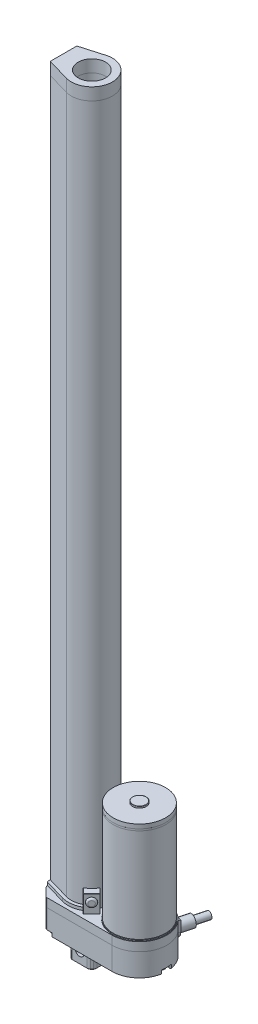
SolidWorks part; units mm, degrees
note: The reader was unsure of these and kept them because the rebuilt part matched: shared geometry of "Sketch1<3>", "Sketch41<11>", "Sketch41<12>", "Sketch45<3>".
ref_plane "Front Plane" through (0, 0, 0) normal (0, 0, 1) x (1, 0, 0)
ref_plane "Top Plane" through (0, 0, 0) normal (0, 1, 0) x (1, 0, 0)
ref_plane "Right Plane" through (0, 0, 0) normal (1, 0, 0) x (0, 0, -1)
sketch "Sketch1" plane through (0, 0, 0) normal (0, 1, 0) x (1, 0, 0)
  line L0 (0, 32.639) -> (7.239, 39.878)
  line L1 (7.239, 0) -> (55.118, 0)
  line L2 (0, 7.239) -> (0, 32.639)
  line L3 (7.239, 39.878) -> (55.118, 39.878)
  line L4 (7.239, 0) -> (0, 7.239)
  arc A0 (55.118, 0) -> (55.118, 39.878) centre (55.118, 19.939) ccw
  point P0 (0, 0)
  point P2 (0, 39.878)
  dimension "D1" = 55.118
  dimension "D2" = 39.878
extrude "Boss-Extrude1" add sketch "Sketch1" along normal blind 6.35
sketch "Sketch6" plane through (0, 6.35, 0) normal (0, 1, 0) x (1, 0, 0)
  circle A0 centre (55.118, 19.939) radius 19.431
extrude "Boss-Extrude4" add sketch "Sketch6" along normal blind 0.762 separate body contours A0
sketch "Sketch7" plane through (0, 7.112, 0) normal (0, 1, 0) x (1, 0, 0)
  circle A0 centre (55.118, 19.939) radius 19.05
  dimension "D1" = 38.1
extrude "Boss-Extrude5" add sketch "Sketch7" along normal blind 68.326 separate body
sketch "Sketch8" plane through (0, 75.438, 0) normal (0, 1, 0) x (1, 0, 0)
  circle A0 centre (55.118, 19.939) radius 4.953
  dimension "D1" = 9.906
fillet "Fillet6" radius 5.08 2 edges at (0, 3.175, -7.239) (0, 3.175, -32.639)
fillet "Fillet7" radius 1.905 2 edges at (7.239, 3.175, -39.878) (7.239, 3.175, 0)
sketch "Sketch15" plane through (0, 6.35, 0) normal (0, 1, 0) x (1, 0, 0)
  line L0 (35.5603, 29.0153) -> (35.5603, 29.0265)
  line L2 (0, 30.5348) -> (0, 9.3432) construction
  line L3 (0, 19.939) -> (0, 10.2869)
  line L4 (0, 19.939) -> (0, 29.591)
  line L5 (0, 10.2869) -> (16.412, 5.5423)
  line L7 (35.5603, 10.8628) -> (35.5603, 10.8515)
  line L10 (0, 29.591) -> (16.4119, 34.3357)
  arc A0 (16.412, 5.5423) -> (16.4119, 34.3357) centre (20.574, 19.939) ccw
ref_plane "Plane4" through (13.8375, 0, -51.6424) normal (0.2588, 0, -0.9659) x (0, -1, 0)
ref_plane "Plane5" through (12.5227, 0, -46.7355) normal (0.2588, 0, -0.9659) x (0, -1, 0)
sketch "Sketch23" plane through (12.5227, 0, -46.7355) normal (0.2588, 0, -0.9659) x (0, -1, 0)
  line L0 (-6.35, -67.5103) -> (-6.35, -28.6483) construction
  line L1 (-2.032, -53.8839) -> (5.588, -53.8839)
  line L2 (-2.032, -53.8839) -> (-2.032, -42.4539)
  line L3 (-2.032, -42.4539) -> (5.588, -42.4539)
  arc A0 (5.588, -53.8839) -> (5.588, -42.4539) centre (5.588, -48.1689) ccw
  dimension "D1" = 11.43
  dimension "D2" = 7.62
  dimension "D3" = 4.318
extrude "Boss-Extrude15" add sketch "Sketch23" along normal blind 6.35
sketch "Sketch24" plane through (14.1662, 0, -52.8692) normal (0.2588, 0, -0.9659) x (-0.9659, 0, -0.2588)
  circle A0 centre (-48.1689, -5.588) radius 4.064
  dimension "D1" = 8.128
extrude "Boss-Extrude16" add sketch "Sketch24" along normal blind 10.16
sketch "Sketch25" plane through (16.7959, 0, -62.683) normal (0.2588, 0, -0.9659) x (-0.9659, 0, -0.2588)
  circle A0 centre (-48.1689, -5.588) radius 2.54
  dimension "D1" = 5.08
extrude "Boss-Extrude17" add sketch "Sketch25" along normal blind 10.16
extrude "Boss-Extrude19" add sketch "Sketch1<3>" against normal blind 16.51 separate body
sketch "Sketch1<3>" plane through (0, 0, 0) normal (0, 1, 0) x (1, 0, 0) same geometry as "Sketch1"
fillet "Fillet13" radius 1.905 2 edges at (7.239, -8.255, 0) (7.239, -8.255, -39.878)
fillet "Fillet14" radius 5.08 2 edges at (0, -8.255, -32.639) (0, -8.255, -7.239)
sketch "Sketch26" plane through (0, -16.51, 0) normal (0, -1, 0) x (-1, 0, 0)
  line L4 (-20.574, 28.829) -> (-11.684, 28.829)
  line L5 (-20.574, 28.829) -> (-29.464, 28.829)
  line L6 (-11.684, 28.829) -> (-11.684, 11.049)
  line L7 (-11.684, 11.049) -> (-29.464, 11.049)
  line L8 (-29.464, 11.049) -> (-29.464, 28.829)
extrude "Boss-Extrude20" add sketch "Sketch26" along normal blind 18.796 separate body
chamfer "Chamfer1" distance 2.54 angle 45 4 edges at (29.464, -25.908, -28.829) (29.464, -25.908, -11.049) (11.684, -25.908, -11.049) (11.684, -25.908, -28.829)
fillet "Fillet15" radius 2.54 8 edges at (11.684, -25.908, -13.589) (14.224, -25.908, -11.049) (26.924, -25.908, -11.049) (29.464, -25.908, -13.589) (29.464, -25.908, -26.289) (26.924, -25.908, -28.829) (11.684, -25.908, -26.289) (14.224, -25.908, -28.829)
chamfer "Chamfer2" distance 0.762 angle 45 16 edges at (14.3041, -35.306, -11.2423) (20.574, -35.306, -11.049) (26.8439, -35.306, -11.2423) (28.194, -35.306, -12.319) (29.2707, -35.306, -13.6691) (29.464, -35.306, -19.939) (29.2707, -35.306, -26.2089) (28.194, -35.306, -27.559) (26.8439, -35.306, -28.6357) (20.574, -35.306, -28.829) (14.3041, -35.306, -28.6357) (12.954, -35.306, -27.559) (11.8773, -35.306, -26.2089) (11.684, -35.306, -19.939) (11.8773, -35.306, -13.6691) (12.954, -35.306, -12.319)
sketch "Sketch27" plane through (0, 0, -11.049) normal (0, 0, 1) x (1, 0, 0)
  circle A0 centre (20.574, -26.67) radius 3.175
extrude "Cut-Extrude3" cut sketch "Sketch27" against normal blind 19.05
sketch "Sketch28" plane through (0, 75.438, 0) normal (0, 1, 0) x (1, 0, 0)
  circle A0 centre (55.118, 19.939) radius 19.05
extrude "Boss-Extrude22" add sketch "Sketch28" along normal blind 1.27 separate body
sketch "Sketch29" plane through (0, 76.708, 0) normal (0, 1, 0) x (1, 0, 0)
  circle A0 centre (55.118, 19.939) radius 19.05
extrude "Boss-Extrude24" add sketch "Sketch29" along normal blind 3.048 separate body contours A0
extrude "Boss-Extrude25" add sketch "Sketch8" along normal blind 1.27 from surface at 4.318 contours A0 starting at face at (55.118, 79.756, -0.889)
fillet "Fillet16" radius 0.2286 1 edges at (55.118, 81.026, -14.986)
extrude "Boss-Extrude26" add sketch "Sketch15" along normal blind 508.381 separate body contours L5 A0 L10 L4 L3
sketch "Sketch32" plane through (0, 514.731, 0) normal (0, 1, 0) x (1, 0, 0)
  line L0 (0, 10.2869) -> (0, 29.591)
  line L1 (0, 29.591) -> (16.4119, 34.3357)
  line L2 (0, 10.2869) -> (16.412, 5.5423)
  arc A0 (16.412, 5.5423) -> (16.4119, 34.3357) centre (20.574, 19.939) ccw
  circle A1 centre (20.574, 19.939) radius 9.9695
  dimension "D1" = 19.939
extrude "Boss-Extrude27" add sketch "Sketch32" along normal blind 8.89 separate body
sketch "Sketch33" plane through (0, 523.621, 0) normal (0, 1, 0) x (1, 0, 0)
  circle A0 centre (20.574, 19.939) radius 10.033
  dimension "D1" = 20.066
sketch3d "3DSketch1" plane through (0, 0, 0) normal (0, 0, 1) x (1, 0, 0)
sketch "Sketch41" plane through (0, 6.35, 0) normal (0, 1, 0) x (1, 0, 0)
  line L0 (16.4119, 34.3357) -> (0, 29.591)
  line L1 (37.5429, 9.0662) -> (33.7712, 12.8379)
  line L2 (0.2737, 32.0497) -> (15.777, 36.5318)
  line L3 (37.5429, 9.0662) -> (31.2567, 2.78)
  line L4 (0, 29.591) -> (0, 30.5348)
  line L5 (0, 30.5348) -> (0.2737, 32.0497)
  line L6 (-0.6349, 31.7871) -> (15.777, 36.5318) construction
  line L7 (0, 19.9389) -> (7.9017, 19.9389)
  line L8 (31.2567, 2.78) -> (27.426, 6.6107)
  line L9 (0, 10.2869) -> (0, 29.591) construction
  line L10 (0, 10.2869) -> (0, 9.3431)
  line L12 (37.5429, 30.8116) -> (33.7712, 27.0399)
  line L13 (37.5429, 30.8116) -> (31.2567, 37.0978)
  line L14 (31.2567, 37.0978) -> (27.426, 33.2671)
  line L15 (0, 9.3431) -> (0.2737, 7.8281)
  line L16 (0.2737, 7.8281) -> (15.777, 3.3461)
  line L17 (16.4119, 5.5422) -> (0, 10.2869)
  line L18 (-0.6349, 8.0908) -> (15.7771, 3.3462) construction
  line L19 (27.426, 33.2671) -> (29.1122, 34.9533)
  line L20 (0, 29.591) -> (16.4119, 34.3357) construction
  line L21 (0, 10.2869) -> (16.412, 5.5423) construction
  arc A0 (16.4119, 34.3357) -> (33.7712, 27.0399) centre (20.574, 19.939) cw
  arc A1 (15.777, 36.5318) -> (29.1122, 34.9533) centre (20.574, 19.939) cw
  arc A2 (16.4119, 34.3357) -> (16.412, 5.5423) centre (20.574, 19.939) cw construction
  arc A3 (15.777, 36.5318) -> (15.7771, 3.3462) centre (20.574, 19.939) cw construction
  arc A4 (16.4119, 34.3357) -> (27.426, 33.2671) centre (20.574, 19.939) cw
  arc A5 (15.777, 3.3461) -> (29.1122, 4.9245) centre (20.574, 19.9389) ccw
  arc A6 (16.4119, 5.5422) -> (33.7712, 12.8379) centre (20.574, 19.9389) ccw
  line M5 (0, 30.5348) -> (0, 9.3432)
  arc M6 (0, 9.3432) -> (1.4879, 5.7511) centre (5.08, 9.3432) ccw
extrude "Boss-Extrude30" add sketch "Sketch41" along normal blind 2.159 separate body contours A1 L2 L5 L0 A0 L14 M5
extrude "Boss-Extrude31" add sketch "Sketch41<11>" along normal blind 2.159 separate body contours A6 L17 L15 L16 A5 L8 M5 M6
sketch "Sketch41<11>" plane through (0, 6.35, 0) normal (0, 1, 0) x (1, 0, 0) same geometry as "Sketch41"
extrude "Boss-Extrude33" add sketch "Sketch41<12>" along normal blind 12.7 separate body contours L14 A0 L12 L13 | A6 L8 L3 L1
sketch "Sketch41<12>" plane through (0, 6.35, 0) normal (0, 1, 0) x (1, 0, 0) same geometry as "Sketch41"
fillet "Fillet17" radius 0.2286 5 edges at (35.657, 19.05, -28.9258) (29.3413, 19.05, -35.1825) (34.3998, 19.05, -33.9547) (37.5429, 12.7, -30.8116) (31.2567, 12.7, -37.0978)
fillet "Fillet18" radius 0.2286 5 edges at (35.657, 19.05, -10.9521) (29.3413, 19.05, -4.6954) (37.5429, 12.7, -9.0662) (34.3998, 19.05, -5.9231) (31.2567, 12.7, -2.78)
sketch "Sketch43" plane through (34.1773, 0, -34.1773) normal (0.7071, 0, -0.7071) x (-0.7071, 0, -0.7071)
  circle A0 centre (-0.3147, 13.7414) radius 3.175
extrude "Boss-Extrude34" add sketch "Sketch43" along normal blind 1.27 separate body
fillet "Fillet19" radius 1.27 1 edges at (33.0527, 13.7414, -37.0978)
sketch "Sketch44" plane through (14.2383, 0, 14.2383) normal (0.7071, 0, 0.7071) x (0.7071, 0, -0.7071)
  circle A0 centre (28.5126, 13.7414) radius 3.175
extrude "Boss-Extrude35" add sketch "Sketch44" along normal blind 1.27 separate body
fillet "Fillet20" radius 1.27 1 edges at (37.5429, 13.7414, -7.2702)
sketch "Sketch45" plane through (0, -16.51, 0) normal (0, -1, 0) x (1, 0, 0)
  line L0 (4.0845, -36.7235) -> (6.681, -39.32)
  line L2 (6.681, -39.32) -> (1.4879, -34.1269) construction
  line L4 (55.118, -39.878) -> (8.0281, -39.878) construction
  line L5 (11.3938, -39.878) -> (8.0281, -39.878)
  line L6 (11.3938, 0) -> (8.0281, 0)
  line L7 (4.0845, -3.1545) -> (6.681, -0.558)
  arc A0 (11.2821, -38.9146) -> (11.3938, -39.878) centre (11.8197, -39.3405) ccw
  arc A1 (11.2821, -38.9146) -> (5.0443, -35.9783) centre (8.8543, -35.9783) ccw
  arc A2 (11.2821, -0.9634) -> (11.3938, 0) centre (11.8197, -0.5375) cw
  arc A3 (5.0443, -35.9783) -> (4.0845, -36.7235) centre (4.1918, -35.871) cw
  arc A4 (5.0443, -3.8997) -> (4.0845, -3.1545) centre (4.1918, -4.007) ccw
  arc A5 (11.2821, -0.9634) -> (5.0443, -3.8997) centre (8.8543, -3.8997) cw
  arc A6 (55.118, -39.878) -> (55.118, 0) centre (55.118, -19.939) ccw construction
  arc A7 (73.6621, -16.9922) -> (73.6621, -22.8858) centre (71.247, -19.939) ccw
  arc A8 (73.6621, -22.8858) -> (74.7121, -23.6317) centre (73.8141, -23.7837) cw
  arc A9 (73.6621, -16.9922) -> (74.7121, -16.2463) centre (73.8141, -16.0943) ccw
  arc A10 (8.0281, -39.878) -> (6.681, -39.32) centre (8.0281, -37.973) cw
  arc A11 (8.0281, 0) -> (6.681, -0.558) centre (8.0281, -1.905) ccw
  arc A12 (74.7121, -23.6317) -> (74.7121, -16.2463) centre (55.118, -19.939) ccw
  line M8 (1.4879, -34.1269) -> (6.681, -39.32)
  arc M9 (6.681, -39.32) -> (8.0281, -39.878) centre (8.0281, -37.973) ccw
  line M10 (8.0281, -39.878) -> (55.118, -39.878)
  line M12 (55.118, 0) -> (8.0281, 0)
  arc M13 (8.0281, 0) -> (6.681, -0.558) centre (8.0281, -1.905) ccw
  line M14 (6.681, -0.558) -> (1.4879, -5.7511)
extrude "Cut-Extrude5" cut sketch "Sketch45" against normal blind 2.54 contours A1 A3 A0 M8 M9 M10 | A5 A2 A4 M12 M13 M14
extrude "Cut-Extrude6" cut sketch "Sketch45<3>" against normal blind 2.54
sketch "Sketch45<3>" plane through (0, -16.51, 0) normal (0, -1, 0) x (1, 0, 0) same geometry as "Sketch45"
sketch "Sketch47" plane through (0, -13.97, 0) normal (0, -1, 0) x (-1, 0, 0)
  circle A0 centre (-8.8543, 35.9783) radius 2.54
  circle A1 centre (-8.8543, 3.8997) radius 2.54
  circle A2 centre (-71.247, 19.939) radius 2.54
extrude "Boss-Extrude36" add sketch "Sketch47" along normal blind 2.54 separate body
fillet "Fillet22" radius 1.524 1 edges at (8.8543, -16.51, -38.5183)
fillet "Fillet23" radius 1.524 1 edges at (8.8543, -16.51, -6.4397)
sketch "Sketch48" plane through (0, 0, 0) normal (-1, 0, 0) x (0, 0, 1)
  circle A0 centre (-19.939, 12.7) radius 3.81
extrude "Boss-Extrude37" add sketch "Sketch48" along normal blind 1.524
fillet "Fillet24" radius 1.524 1 edges at (-1.524, 12.7, -16.129)
fillet "Fillet25" radius 1.524 1 edges at (71.247, -16.51, -22.479)
sketch "Sketch49" plane through (0, 0, 0) normal (-1, 0, 0) x (0, 0, 1)
  line L0 (-19.9389, 514.731) -> (-19.9389, 509.778) construction
  line L1 (-29.591, 514.731) -> (-10.2869, 514.731) construction
  line L2 (-30.5348, 6.35) -> (-9.3432, 6.35) construction
  circle A0 centre (-19.9389, 509.778) radius 3.81
  dimension "Flat Head Screw" = 503.428
extrude "Cut-Extrude7" cut sketch "Sketch49" against normal blind 2.54
sketch "Sketch50" plane through (2.54, 0, 0) normal (-1, 0, 0) x (0, 0, 1)
  circle A0 centre (-19.9389, 509.778) radius 3.556
extrude "Boss-Extrude39" add sketch "Sketch50" along normal blind 2.54 contours A0
sketch "Sketch52" plane through (0, 0, -11.049) normal (0, 0, 1) x (1, 0, 0)
  circle A0 centre (20.574, 535.432) radius 3.175
  circle A1 centre (20.574, -26.67) radius 3.175 construction
  dimension "Hole to Hole" = 562.102
extrude "Cut-Extrude8" cut sketch "Sketch33" against normal blind 488.95
scale "Scale1" bodies to scale 135 124 133 143 151 144 149 101 148 107 145 106 128 141 146 161 142 150 130 scale about origin uniform scaling yes scale factor 0.25
equation "\"Stroke\"= 18"
equation "\"D1@Boss-Extrude26\"= \"Stroke\" + 2.015"
equation "\"Flat Head Screw@Sketch49\"= \"Stroke\" + 1.82"
equation "\"Hole to Hole@Sketch52\"= \"Stroke\" + 4.13"
